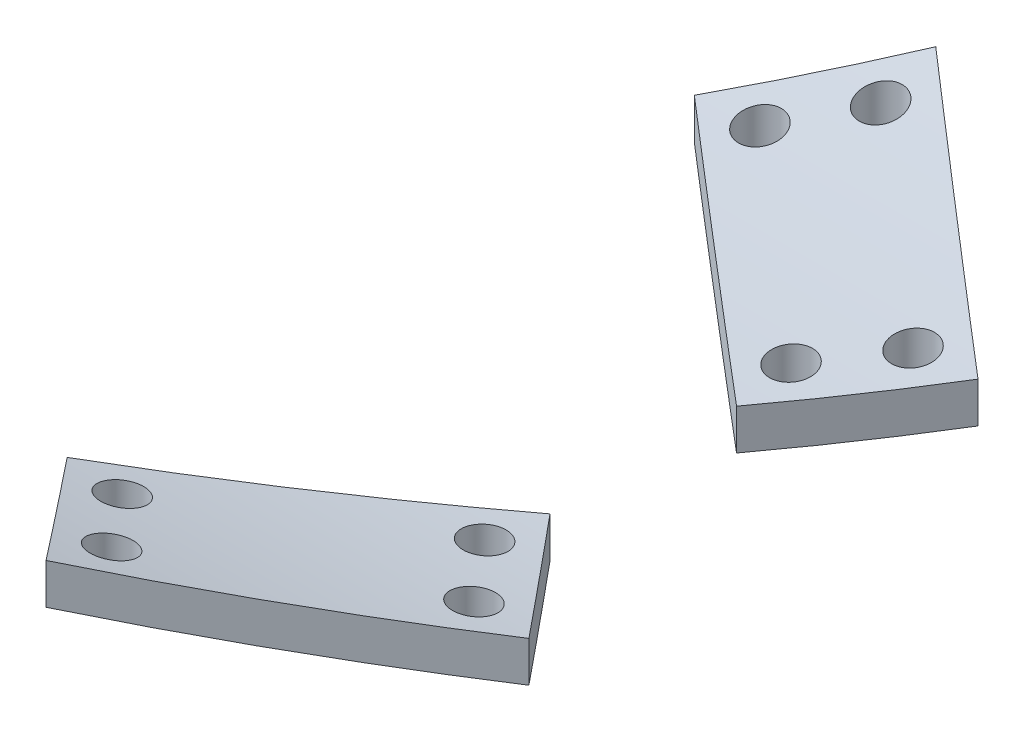
SolidWorks part; units mm, degrees
ref_plane "Front Plane" through (0, 0, 0) normal (0, 0, 1) x (1, 0, 0)
ref_plane "Top Plane" through (0, 0, 0) normal (0, 1, 0) x (1, 0, 0)
ref_plane "Right Plane" through (0, 0, 0) normal (1, 0, 0) x (0, 0, -1)
sketch "Sketch3" plane through (0, 0, 0) normal (1, 0, 0) x (0, 0, -1)
  line L0 (-8.3933, 1.9614) -> (-8.3933, -4.052)
  line L6 (-8.3933, -4.3886) -> (-8.3933, 1.9614)
  line L8 (232.9067, -4.3886) -> (232.9067, 1.9614)
  line L9 (232.9067, -4.052) -> (232.9067, 1.9614)
  arc A2 (-8.3933, 1.9614) -> (232.9067, 1.9614) centre (112.2567, 210.9333) ccw
  arc A3 (-8.3933, -4.052) -> (232.9067, -4.052) centre (112.2567, 204.9199) ccw
  dimension "D1" = 6.35
  dimension "D2" = 241.3
extrude "Boss-Extrude4" add sketch "Sketch3" along normal blind 304.8 contours L0 A3 L8 A2 region at (0, -32.81, -112.2567)
ref_plane "Plane1" through (0, 1.9614, 0) normal (0, 1, 0) x (1, 0, 0)
sketch "Sketch4" plane through (0, 1.9614, 0) normal (0, 1, 0) x (1, 0, 0)
  line L0 (209.1319, 158.7335) -> (225.4588, 178.191)
  line L2 (209.1319, 158.7335) -> (248.047, 126.0799)
  line L3 (225.4588, 178.191) -> (264.3738, 145.5374)
  line L4 (248.047, 126.0799) -> (264.3738, 145.5374)
  line L5 (209.1319, 158.7335) -> (225.4588, 178.191)
  line L6 (209.1319, 158.7335) -> (248.047, 126.0799)
  line L7 (225.4588, 46.3224) -> (209.1319, 65.7799)
  line L8 (225.4588, 46.3224) -> (264.3738, 78.976)
  line L9 (209.1319, 65.7799) -> (248.047, 98.4335)
  line L10 (264.3738, 78.976) -> (248.047, 98.4335)
  line L11 (209.1319, 158.7335) -> (248.047, 126.0799)
  line L12 (264.3738, 145.5374) -> (248.047, 126.0799)
  line L13 (225.4588, 178.191) -> (264.3738, 145.5374)
  line L14 (225.4588, 178.191) -> (209.1319, 158.7335)
  line L15 (209.1319, 65.7799) -> (214.4602, 59.4299)
  line L16 (209.1319, 65.7799) -> (213.9963, 69.8616)
  line L17 (225.4588, 178.191) -> (264.3738, 145.5374)
  line L18 (248.047, 126.0799) -> (264.3738, 145.5374)
  line L23 (167.7803, 8.3841) -> (167.7803, 208.1048)
  line L24 (167.7803, 8.3841) -> (288.1477, 8.3841)
  line L25 (167.7803, 208.1048) -> (288.1477, 208.1048)
  line L26 (288.1477, 8.3841) -> (288.1477, 208.1048)
  circle A0 centre (218.078, 64.9972) radius 3.175
  circle A1 centre (247.2382, 89.5531) radius 3.175
  circle A2 centre (226.2414, 55.2684) radius 3.175
  circle A3 centre (255.4879, 79.7215) radius 3.175
  circle A4 centre (226.2414, 169.2449) radius 3.175
  circle A5 centre (255.4879, 144.7919) radius 3.175
  circle A6 centre (218.078, 159.5162) radius 3.175
  circle A7 centre (247.2382, 134.9602) radius 3.175
  dimension "D3" = 25.4
  dimension "D4" = 50.8
  dimension "D5" = 6.35
  dimension "D6" = 6.35
extrude "Cut-Extrude20" cut sketch "Sketch4" against normal blind 200 contours L24 L26 L25 L23 L4 L2 L0 L3 L10 L8 L7 L9 region at (226.9071, 1.9614, -107.7619) body kept at (225.4588, -21.1838, -178.191) body kept at (209.1319, -25.8485, -65.7799)
extrude "Cut-Extrude21" cut sketch "Sketch4<17>" against normal blind 200 contours A1 | A0 | A6 | A4 | A5 | A7 | A3 | A2
sketch "Sketch4<17>" plane through (0, 1.9614, 0) normal (0, 1, 0) x (1, 0, 0) same geometry as "Sketch4"
